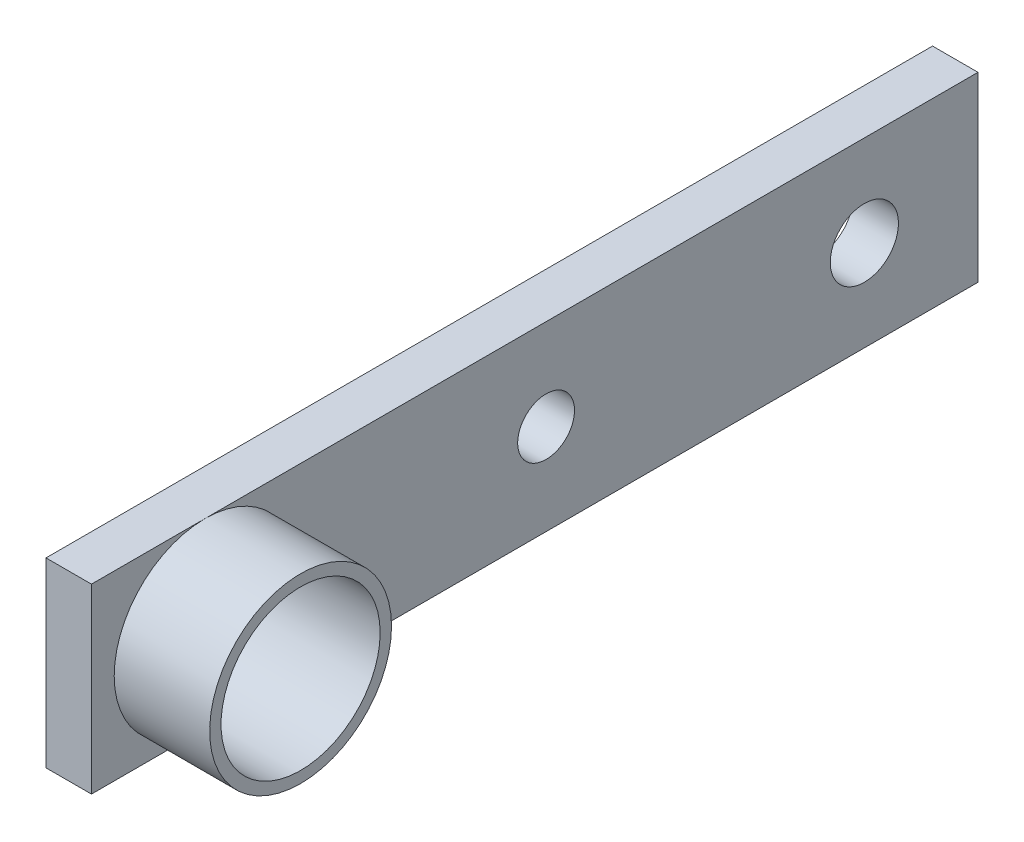
SolidWorks part; units mm, degrees
ref_plane "Front Plane" through (0, 0, 0) normal (0, 0, 1) x (1, 0, 0)
ref_plane "Top Plane" through (0, 0, 0) normal (0, 1, 0) x (1, 0, 0)
ref_plane "Right Plane" through (0, 0, 0) normal (1, 0, 0) x (0, 0, -1)
sketch "Sketch1" plane through (0, 0, 0) normal (1, 0, 0) x (0, 0, -1)
  line L0 (0, 12.7) -> (123.825, 12.7) construction
  line L1 (0, 0) -> (123.825, 0)
  line L2 (0, 0) -> (0, 25.4)
  line L3 (0, 25.4) -> (123.825, 25.4)
  line L4 (123.825, 0) -> (123.825, 25.4)
  circle A0 centre (15.875, 12.7) radius 11.1125
  circle A1 centre (63.5, 12.7) radius 3.9687
  circle A2 centre (107.95, 12.7) radius 4.7625
  dimension "D3" = 22.225
  dimension "D6" = 7.9375
  dimension "D8" = 9.525
  dimension "D1" = 25.4
  dimension "D4" = 15.875
  dimension "D5" = 47.625
  dimension "D7" = 44.45
  dimension "D2" = 15.875
extrude "Boss-Extrude1" add sketch "Sketch1" along normal blind 6.35
sketch "Sketch3" plane through (6.35, 0, 0) normal (1, 0, 0) x (0, 0, -1)
  circle A0 centre (15.875, 12.7) radius 12.7
  circle A1 centre (15.875, 12.7) radius 11.1125 construction
  circle A2 centre (15.875, 12.7) radius 11.1125
  dimension "D1" = 25.4
extrude "Boss-Extrude2" add sketch "Sketch3" along normal blind 13.335
equation "\"D2@Sketch1\"=\"D4@Sketch1\""
